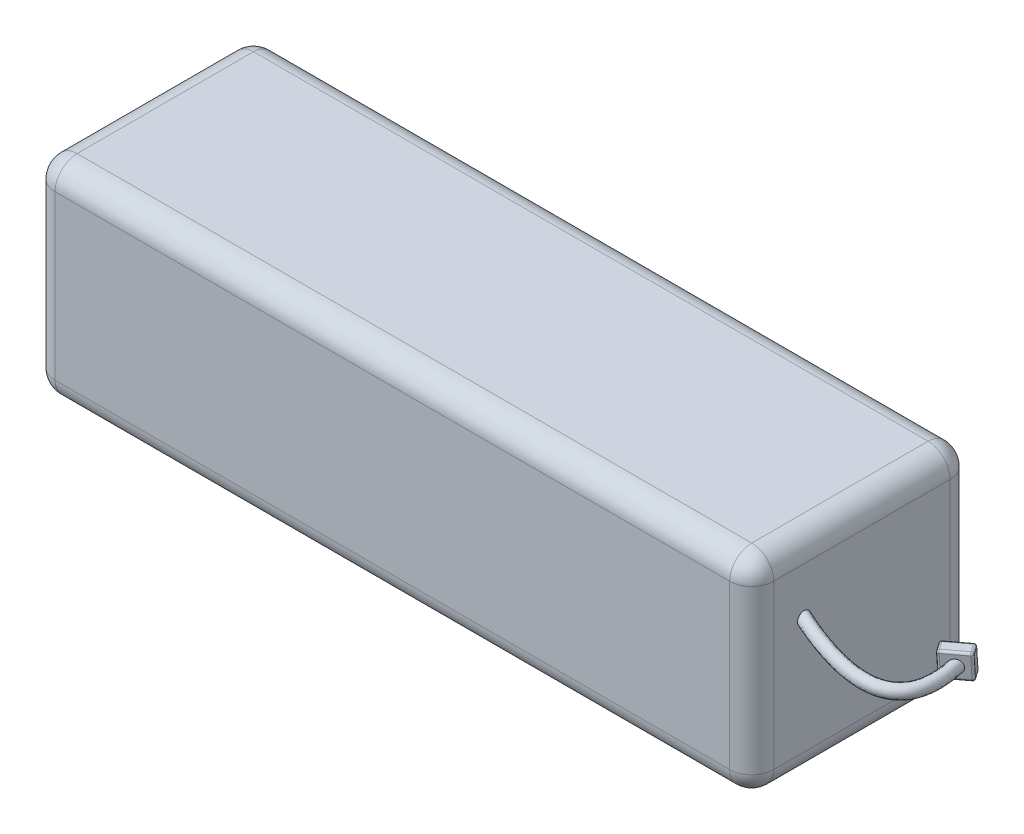
SolidWorks part; units mm, degrees
ref_plane "Front Plane" through (0, 0, 0) normal (0, 0, 1) x (1, 0, 0)
ref_plane "Top Plane" through (0, 0, 0) normal (0, 1, 0) x (1, 0, 0)
ref_plane "Right Plane" through (0, 0, 0) normal (1, 0, 0) x (0, 0, -1)
sketch "Sketch1" plane through (0, 0, 0) normal (0, 0, 1) x (1, 0, 0)
  line L1 (-81.5, -23.5) -> (81.5, -23.5)
  line L2 (-81.5, -23.5) -> (-81.5, 23.5)
  line L3 (-81.5, 23.5) -> (81.5, 23.5)
  line L4 (81.5, -23.5) -> (81.5, 23.5)
  line L5 (-81.5, -23.5) -> (81.5, 23.5) construction
  line L6 (-81.5, 23.5) -> (81.5, -23.5) construction
  point P0 (0, 0)
  dimension "D1" = 47
  dimension "D2" = 163
extrude "Boss-Extrude1" add sketch "Sketch1" along normal blind 50
fillet "Fillet1" radius 5 12 edges at (81.5, 0, 50) (81.5, 23.5, 25) (81.5, 0, 0) (-81.5, 0, 0) (-81.5, 23.5, 25) (-81.5, -23.5, 25) (-81.5, 0, 50) (81.5, -23.5, 25) (0, -23.5, 50) (0, -23.5, 0) (0, 23.5, 0) (0, 23.5, 50)
sketch "Sketch3" plane through (81.5, 0, 0) normal (1, 0, 0) x (0, 0, -1)
  circle A0 centre (-38.1222, 7.7831) radius 1.5
  dimension "D1" = 3
sketch3d "3DSketch3"
  spline S0 degree 2 poles (81.5, 7.7831, 38.1222) (111.7508, 6.8098, 51.2015) (107.6541, 7.2712, 29.9275) knots 0 0 0 1 1 1
sweep "Sweep2" add profiles "Sketch3" path "3DSketch3"
sketch "Sketch4" plane through (47.7434, -4.4811, 70.0236) normal (-0.5626, 0.0528, -0.8251) x (-0.8268, -0.0359, 0.5614)
  line L1 (-75.5424, 12.0596) -> (-69.3861, 12.0596)
  line L2 (-75.5424, 12.0596) -> (-75.5424, 6.2757)
  line L3 (-75.5424, 6.2757) -> (-69.3861, 6.2757)
  line L4 (-69.3861, 12.0596) -> (-69.3861, 6.2757)
  line L5 (-75.5424, 12.0596) -> (-69.3861, 6.2757) construction
  line L6 (-75.5424, 6.2757) -> (-69.3861, 12.0596) construction
  point P0 (-72.4642, 9.1676)
extrude "Boss-Extrude2" add sketch "Sketch4" along normal blind 3
fillet "Fillet2" radius 0.5 12 edges at (107.6541, 4.3852, 29.7428) (104.2654, 4.3538, 30.2332) (105.1092, 7.1606, 31.6555) (103.4215, 7.319, 29.1803) (104.2654, 10.1259, 30.6026) (105.9664, 10.3157, 27.6369) (107.6541, 10.1573, 30.1122) (110.199, 7.3818, 28.1994) (108.5113, 7.5402, 25.7242) (105.9664, 4.5436, 27.2676) (109.3551, 4.5749, 26.7771) (109.3551, 10.3471, 27.1465)
